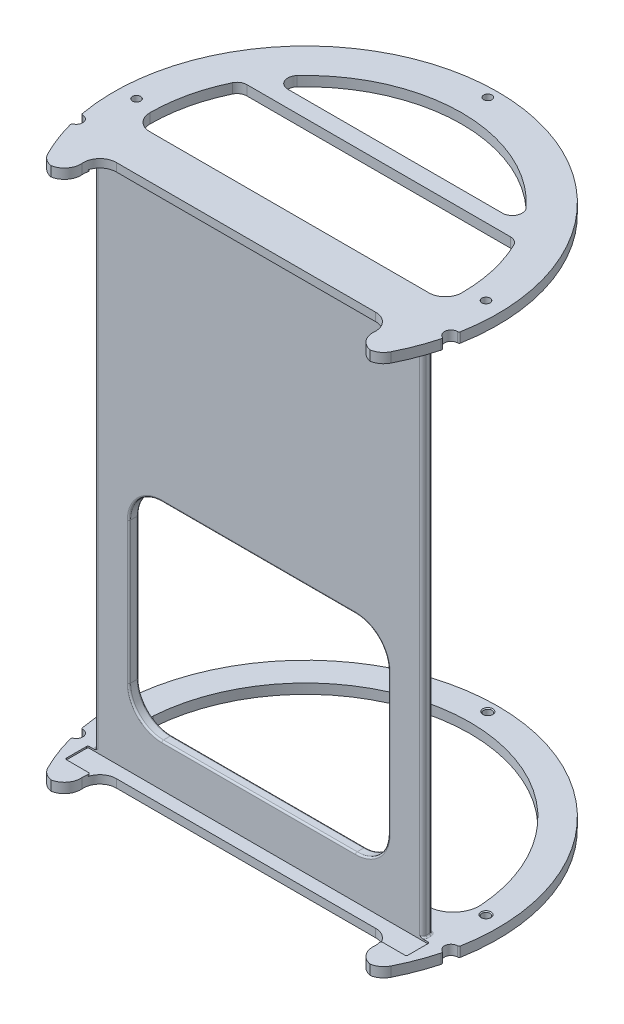
SolidWorks part; units mm, degrees
ref_plane "前视基准面" through (0, 0, 0) normal (0, 0, 1) x (1, 0, 0)
ref_plane "上视基准面" through (0, 0, 0) normal (0, 1, 0) x (1, 0, 0)
ref_plane "右视基准面" through (0, 0, 0) normal (1, 0, 0) x (0, 0, -1)
other "Configuration Table"
sketch "草图2" plane through (0, 0, 0) normal (0, 1, 0) x (1, 0, 0)
  circle A0 centre (0, 0) radius 58.5
  dimension "D1" = 117
extrude "凸台-拉伸1" add sketch "草图2" along normal blind 3
sketch "草图3" plane through (0, 0, 0) normal (0, -1, 0) x (1, 0, 0)
  line L0 (-47.2361, 5) -> (47.2361, 5)
  arc A0 (-47.2361, 5) -> (47.2361, 5) centre (0, 0) ccw
  dimension "D1" = 95
  dimension "D2" = 5
extrude "切除-拉伸2" cut sketch "草图3" against normal through all
sketch "草图4" plane through (0, 0, 0) normal (0, -1, 0) x (-1, 0, 0)
  line L1 (-46.5639, -18.2154) -> (46.5639, -18.2154)
  arc A1 (-46.5639, -18.2154) -> (46.5639, -18.2154) centre (0, 0) ccw
  dimension "D1" = 100
extrude "切除-拉伸3" cut sketch "草图4" against normal through all
sketch "草图5" plane through (0, 0, 0) normal (0, 1, 0) x (1, 0, 0)
  line L1 (-53.5909, -87.9382) -> (53.5909, -87.9382)
  line L2 (-53.5909, -87.9382) -> (-53.5909, -29.0618)
  line L3 (-53.5909, -29.0618) -> (53.5909, -29.0618)
  line L4 (53.5909, -87.9382) -> (53.5909, -29.0618)
  line L5 (-53.5909, -87.9382) -> (53.5909, -29.0618) construction
  line L6 (-53.5909, -29.0618) -> (53.5909, -87.9382) construction
  circle A0 centre (0, 0) radius 58.5 construction
  point P0 (0, -58.5)
extrude "切除-拉伸8" cut sketch "草图5" along normal through all
fillet "圆角2" radius 5 4 edges at (-50.7707, 1.5, 29.0618) (-40.6868, 1.5, 29.0618) (50.7707, 1.5, 29.0618) (40.6868, 1.5, 29.0618)
sketch "草图6" plane through (0, 0, 0) normal (0, -1, 0) x (1, 0, 0)
  line L34 (49, 14.34) -> (-49, 14.34)
  line L35 (-50, 13.34) -> (-50, 12.34)
  line L36 (-49, 11.34) -> (49, 11.34)
  line L37 (50, 12.34) -> (50, 13.34)
  arc A9 (49, 11.34) -> (50, 12.34) centre (49, 12.34) ccw
  arc A11 (50, 13.34) -> (49, 14.34) centre (49, 13.34) ccw
  arc A13 (-49, 14.34) -> (-50, 13.34) centre (-49, 13.34) ccw
  arc A15 (-50, 12.34) -> (-49, 11.34) centre (-49, 12.34) ccw
  point P0 (-0.7773, 15.5362)
extrude "切除-拉伸9" cut sketch "草图6" against normal through all
fillet "圆角4" radius 5 2 edges at (47.2361, 1.5, 5) (-47.2361, 1.5, 5)
sketch "草图7" plane through (0, 0, 0) normal (0, -1, 0) x (1, 0, 0)
  line L1 (-42.6248, -22.2056) -> (42.6248, -22.2056)
  line L2 (-42.6248, -22.2056) -> (-42.6248, -27.2056)
  line L3 (-42.6248, -27.2056) -> (42.6248, -27.2056)
  line L4 (42.6248, -22.2056) -> (42.6248, -27.2056)
  line L5 (-42.6248, -22.2056) -> (42.6248, -27.2056) construction
  line L6 (-42.6248, -27.2056) -> (42.6248, -22.2056) construction
  point P0 (0, -24.7056)
  dimension "D1" = 5
extrude "凸台-拉伸2" add sketch "草图7" against normal up to surface (3 mm away) up to face at (0, 3, 12.84)
fillet "圆角5" radius 3 4 edges at (-41.99, 1.5, -22.2056) (41.99, 1.5, -22.2056) (38.9372, 1.5, -27.2056) (-38.9372, 1.5, -27.2056)
fillet "圆角7" radius 5 2 edges at (46.5639, 1.5, 18.2154) (-46.5639, 1.5, 18.2154)
sketch "草图8" plane through (0, 0, 0) normal (0, -1, 0) x (1, 0, 0)
  line L0 (-51.5, 20.84) -> (-51.5, 14.2873) construction
  line L1 (-51.5, 14.2873) -> (51.5, 14.2873) construction
  line L2 (51.5, 14.2873) -> (51.5, 20.84) construction
  line L3 (51.5, 20.84) -> (-51.5, 20.84) construction
  line L4 (52, 21.34) -> (-52, 21.34)
  line L5 (-52, 21.34) -> (-52, 13.7873)
  line L6 (-52, 13.7873) -> (52, 13.7873)
  line L7 (52, 13.7873) -> (52, 21.34)
  point P2 (0, 13.7873)
  dimension "D1" = 0.5
extrude "切除-拉伸10" cut sketch "草图8" against normal blind 0.5
fillet "圆角8" radius 0.5 6 edges at (52, 0.25, 13.7873) (52, 0.25, 21.34) (44.1282, 0.25, 21.34) (-44.1282, 0.25, 21.34) (-52, 0.25, 21.34) (-52, 0.25, 13.7873)
sketch "草图9" plane through (0, 0, 0) normal (0, -1, 0) x (1, 0, 0)
  line L0 (-32.6783, -27.2056) -> (32.6783, -27.2056) construction
  line L1 (-32.6783, -27.2056) -> (32.6783, -27.2056)
  line L3 (-32.6783, -22.2056) -> (32.6783, -22.2056)
  arc A0 (34.8813, -32.2419) -> (32.6783, -27.2056) centre (32.6783, -30.2056) ccw construction
  arc A1 (-34.8813, -32.2419) -> (34.8813, -32.2419) centre (0, 0) ccw construction
  arc A2 (-32.6783, -27.2056) -> (-34.8813, -32.2419) centre (-32.6783, -30.2056) ccw construction
  arc A3 (34.8813, -32.2419) -> (32.6783, -27.2056) centre (32.6783, -30.2056) ccw
  arc A4 (-34.8813, -32.2419) -> (34.8813, -32.2419) centre (0, 0) ccw
  arc A5 (-32.6783, -27.2056) -> (-34.8813, -32.2419) centre (-32.6783, -30.2056) ccw
  arc A9 (38.5531, -35.6358) -> (32.6783, -22.2056) centre (32.6783, -30.2056) ccw
  arc A10 (-38.5531, -35.6358) -> (38.5531, -35.6358) centre (0, 0) ccw
  arc A11 (-32.6783, -22.2056) -> (-38.5531, -35.6358) centre (-32.6783, -30.2056) ccw
  dimension "D1" = 5
sketch "草图10" plane through (0, 0, 0) normal (0, -1, 0) x (1, 0, 0)
  line L0 (40.1422, -22.2056) -> (-40.1422, -22.2056) construction
  line L1 (-40.1422, -27.22) -> (40.1422, -27.22)
  line L2 (-40.1422, -27.22) -> (-40.1422, -22.2056)
  line L3 (-40.1422, -22.2056) -> (40.1422, -22.2056)
  line L4 (40.1422, -27.22) -> (40.1422, -22.2056)
  line L5 (-40.1422, -27.22) -> (40.1422, -22.2056) construction
  line L6 (-40.1422, -22.2056) -> (40.1422, -27.22) construction
  arc A0 (40.1422, -22.2056) -> (42.8484, -20.5004) centre (40.1422, -19.2056) ccw construction
  point P0 (0, -24.7128)
extrude "凸台-拉伸3" add sketch "草图10" against normal up to surface (3 mm away) up to face at (0, 3, -9.3304)
sketch "草图11" plane through (0, 3, 0) normal (0, 1, 0) x (1, 0, 0)
  circle A0 centre (-57.0735, -12.84) radius 2
  arc A1 (52.2495, -26.3105) -> (-52.2495, -26.3105) centre (0, 0) ccw construction
  circle A2 centre (57.0735, -12.84) radius 2
  arc A3 (52.2495, -26.3105) -> (-52.2495, -26.3105) centre (0, 0) ccw construction
  dimension "D1" = 4
  dimension "D2" = 4
extrude "切除-拉伸11" cut sketch "草图11" against normal blind 10
fillet "圆角9" radius 0.5 4 edges at (-56.6012, 1.5, 14.7834) (-57.4791, 1.5, 10.8816) (56.6012, 1.5, 14.7834) (57.4791, 1.5, 10.8816)
sketch "草图12" plane through (0, 0, 0) normal (0, -1, 0) x (1, 0, 0)
  point P0 (53.2134, -1.6686)
  point P1 (-0.0866, -55.5261)
  point P3 (-53.2134, -1.6686)
hole_wizard "M3 螺纹孔1" positions "草图12" profile "草图13" tap size "M3" standard "GB"
sketch "草图13" plane through (53.2134, 0, -1.6686) normal (1, 0, 0) x (0, 0, -1)
  line L0 (0, 0) -> (0, 4.6511)
  line L1 (0, 4.6511) -> (1.25, 3.9)
  line L2 (1.25, 3.9) -> (1.25, 0.275)
  line L3 (1.25, 0.275) -> (1.525, 0)
  line L5 (1.525, 0) -> (0, 0)
  line L6 (-1.25, 0.275) -> (-1.525, 0) construction
  line L10 (0, 4.6511) -> (-1.25, 3.9) construction
  line L11 (0, -6.35) -> (0, 107.95) construction
  dimension "螺纹孔钻头直径" = 2.5
  dimension "螺纹孔钻头深度" = 3.9
  dimension "近端锥形沉头孔直径" = 3.05
  dimension "近端锥形沉头孔角度" = 90
  dimension "导头角度" = 118
cosmetic thread "孔螺蚊线1" parameters "D1"=2.4, "D2"=3
cosmetic thread "孔螺蚊线2" parameters "D1"=2.4, "D2"=3
cosmetic thread "孔螺蚊线3" parameters "D1"=2.4, "D2"=3
sketch "草图16" plane through (0, 3, 0) normal (0, 1, 0) x (1, 0, 0)
  line L0 (50, -12.34) -> (50, -13.34) construction
  line L1 (49, -14.34) -> (-49, -14.34) construction
  line L2 (-49, -11.34) -> (49, -11.34) construction
  line L3 (-50, -13.34) -> (-50, -12.34) construction
  line L4 (50, -12.34) -> (50, -13.34)
  line L5 (49, -14.34) -> (-49, -14.34)
  line L6 (-49, -11.34) -> (49, -11.34)
  line L7 (-50, -13.34) -> (-50, -12.34)
  arc A0 (49, -14.34) -> (50, -13.34) centre (49, -13.34) ccw construction
  arc A1 (50, -12.34) -> (49, -11.34) centre (49, -12.34) ccw construction
  arc A2 (-49, -11.34) -> (-50, -12.34) centre (-49, -12.34) ccw construction
  arc A3 (-50, -13.34) -> (-49, -14.34) centre (-49, -13.34) ccw construction
  arc A4 (49, -14.34) -> (50, -13.34) centre (49, -13.34) ccw
  arc A5 (50, -12.34) -> (49, -11.34) centre (49, -12.34) ccw
  arc A6 (-49, -11.34) -> (-50, -12.34) centre (-49, -12.34) ccw
  arc A7 (-50, -13.34) -> (-49, -14.34) centre (-49, -13.34) ccw
extrude "凸台-拉伸4" add sketch "草图16" against normal blind 165 separate body
sketch "草图17" plane through (0, 0.5, 0) normal (0, -1, 0) x (1, 0, 0)
sketch "草图18" plane through (0, 0, 14.34) normal (0, 0, 1) x (1, 0, 0)
  line L1 (-38.5, -91) -> (38.5, -91)
  line L2 (-38.5, -91) -> (-38.5, -149)
  line L3 (-38.5, -149) -> (38.5, -149)
  line L4 (38.5, -91) -> (38.5, -149)
  line L5 (-38.5, -91) -> (38.5, -149) construction
  line L6 (-38.5, -149) -> (38.5, -91) construction
  point P0 (0, -120)
  dimension "D1" = 77
  dimension "D2" = 58
  dimension "D3" = 120
ref_plane "基准面3" through (0, -79.5, 0) normal (0, 1, 0) x (1, 0, 0)
mirror "镜向9" about plane through (0, -79.5, 0) normal (0, 1, 0) of bodies 117
combine bodies "组合1" operation type add bodies to combine 120 117 125
sketch "草图20" plane through (0, -159.5, 0) normal (0, 1, 0) x (1, 0, 0)
  line L0 (-49, -14.34) -> (-52, -14.34)
  line L1 (-52, -20.84) -> (-52, -14.2873) construction
  line L2 (49, -14.34) -> (52, -14.34)
  line L3 (52, -14.2873) -> (52, -20.84) construction
  line L4 (49.8944, -13.7873) -> (51.5, -13.7873) construction
  line L5 (52, -14.2873) -> (52, -14.34)
  line L6 (49.8944, -13.7873) -> (51.5, -13.7873)
  line L7 (-51.5, -13.7873) -> (-49.8944, -13.7873) construction
  line L8 (-52, -14.34) -> (-52, -14.2873)
  line L9 (-51.5, -13.7873) -> (-49.8944, -13.7873)
  arc A0 (52, -14.2873) -> (51.5, -13.7873) centre (51.5, -14.2873) ccw construction
  arc A1 (49, -14.34) -> (49.8944, -13.7873) centre (49, -13.34) ccw construction
  arc A2 (52, -14.2873) -> (51.5, -13.7873) centre (51.5, -14.2873) ccw
  arc A3 (49, -14.34) -> (49.8944, -13.7873) centre (49, -13.34) ccw
  arc A4 (-51.5, -13.7873) -> (-52, -14.2873) centre (-51.5, -14.2873) ccw construction
  arc A5 (-49.8944, -13.7873) -> (-49, -14.34) centre (-49, -13.34) ccw construction
  arc A6 (-51.5, -13.7873) -> (-52, -14.2873) centre (-51.5, -14.2873) ccw
  arc A7 (-49.8944, -13.7873) -> (-49, -14.34) centre (-49, -13.34) ccw
extrude "凸台-拉伸6" add sketch "草图20" along normal up to surface (0.5 mm away) up to face at (53.2134, -159, -3.1936)
sketch "草图21" plane through (0, 0.5, 0) normal (0, -1, 0) x (1, 0, 0)
  line L0 (49, 14.34) -> (52, 14.34)
  line L1 (52, 14.2873) -> (52, 20.84) construction
  line L2 (49.8944, 13.7873) -> (51.5, 13.7873) construction
  line L3 (52, 14.2873) -> (52, 14.34)
  line L4 (49.8944, 13.7873) -> (51.5, 13.7873)
  line L5 (-49, 14.34) -> (-52, 14.34)
  line L7 (-52, 20.84) -> (-52, 14.2873) construction
  line L8 (-51.5, 13.7873) -> (-49.8944, 13.7873) construction
  line L9 (-52, 14.34) -> (-52, 14.2873)
  line L10 (-51.5, 13.7873) -> (-49.8944, 13.7873)
  arc A0 (51.5, 13.7873) -> (52, 14.2873) centre (51.5, 14.2873) ccw construction
  arc A1 (50, 13.34) -> (49, 14.34) centre (49, 13.34) ccw construction
  arc A2 (51.5, 13.7873) -> (52, 14.2873) centre (51.5, 14.2873) ccw
  arc A3 (49.8944, 13.7873) -> (49, 14.34) centre (49, 13.34) ccw
  arc A4 (-52, 14.2873) -> (-51.5, 13.7873) centre (-51.5, 14.2873) ccw construction
  arc A5 (-49, 14.34) -> (-50, 13.34) centre (-49, 13.34) ccw construction
  arc A6 (-52, 14.2873) -> (-51.5, 13.7873) centre (-51.5, 14.2873) ccw
  arc A7 (-49, 14.34) -> (-49.8944, 13.7873) centre (-49, 13.34) ccw
extrude "凸台-拉伸7" add sketch "草图21" along normal up to surface (0.5 mm away) up to face at (53.2134, 0, -3.1936)
fillet "圆角13" radius 0.5 18 edges at (-49.7071, -159, 14.0471) (-50, -159, 12.84) (-49.7071, -159, 11.6329) (0, -159, 11.34) (49.7071, -159, 11.6329) (50, -159, 12.84) (-49.7071, 0, 14.0471) (-50, 0, 12.84) (-49.7071, 0, 11.6329) (0, 0, 11.34) (49.7071, 0, 11.6329) (50, 0, 12.84) (49.7071, -159, 14.0471) (52, -159.25, 14.34) (-52, -159.25, 14.34) (49.7071, 0, 14.0471) (52, 0.25, 14.34) (-52, 0.25, 14.34)
sketch "草图22" plane through (0, 0, 11.34) normal (0, 0, -1) x (-1, 0, 0)
  line L1 (-39.5, -83.5) -> (39.5, -83.5)
  line L2 (-39.5, -83.5) -> (-39.5, -146.5)
  line L3 (-39.5, -146.5) -> (39.5, -146.5)
  line L4 (39.5, -83.5) -> (39.5, -146.5)
  line L5 (-39.5, -83.5) -> (39.5, -146.5) construction
  line L6 (-39.5, -146.5) -> (39.5, -83.5) construction
  point P0 (0, -115)
  dimension "D1" = 79
  dimension "D2" = 63
  dimension "D3" = 115
extrude "切除-拉伸13" cut sketch "草图22" against normal blind 83
fillet "圆角14" radius 10 4 edges at (39.5, -83.5, 12.84) (-39.5, -83.5, 12.84) (39.5, -146.5, 12.84) (-39.5, -146.5, 12.84)
fillet "圆角15" radius 0.5 16 edges at (0, -83.5, 14.34) (-36.5711, -86.4289, 14.34) (-39.5, -115, 14.34) (-36.5711, -143.5711, 14.34) (0, -146.5, 14.34) (36.5711, -143.5711, 14.34) (39.5, -115, 14.34) (-36.5711, -86.4289, 11.34) (-39.5, -115, 11.34) (-36.5711, -143.5711, 11.34) (0, -146.5, 11.34) (36.5711, -143.5711, 11.34) (39.5, -115, 11.34) (36.5711, -86.4289, 11.34) (36.5711, -86.4289, 14.34) (0, -83.5, 11.34)
sketch "草图23" plane through (0, -162, 0) normal (0, -1, 0) x (1, 0, 0)
  line L0 (0, 5) -> (49.7494, 5)
  line L1 (42.5, 5) -> (-42.5, 5) construction
  line L2 (0, 5) -> (-49.7494, 5)
  arc A0 (-49.7494, 5) -> (49.7494, 5) centre (0, 0) ccw
  dimension "D1" = 100
extrude "切除-拉伸14" cut sketch "草图23" against normal blind 83
fillet "圆角16" radius 8 2 edges at (49.7494, -160.5, 5) (-49.7494, -160.5, 5)
